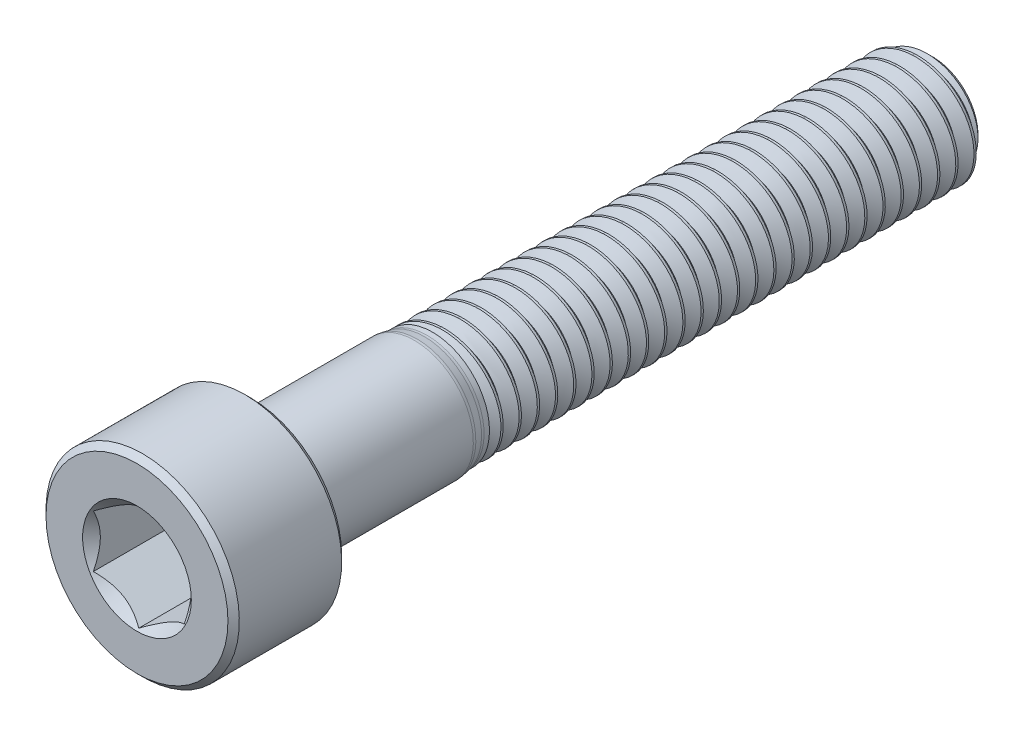
SolidWorks part; units mm, degrees
ref_plane "Front Plane" through (0, 0, 0) normal (0, 0, 1) x (1, 0, 0)
ref_plane "Top Plane" through (0, 0, 0) normal (0, 1, 0) x (1, 0, 0)
ref_plane "Right Plane" through (0, 0, 0) normal (1, 0, 0) x (0, 0, -1)
sketch "Sketch1" plane through (0, 0, 0) normal (1, 0, 0) x (0, 0, -1)
  line L0 (-17.5, 0) -> (17.5, 0) construction
  line L1 (17.5, 0) -> (17.5, 1.9804) construction
  line L2 (17.5, 1.9804) -> (16.9804, 2.5) construction
  line L3 (16.9804, 2.5) -> (16.9, 2.5) construction
  line L4 (16.9, 2.5) -> (-12.5, 2.5) construction
  line L5 (-12.5, 2.5) -> (-12.5, 4.25) construction
  line L6 (-12.5, 4.25) -> (-17.5, 4.25) construction
  line L7 (-17.5, 4.25) -> (-17.5, 0) construction
  line L8 (17.5, 1.9804) -> (17.5, 2.5) construction
  line L9 (17.45, 2.5866) -> (17.85, 1.8938) construction
  line L10 (17.85, 1.8938) -> (18.25, 2.5866) construction
  line L11 (18.25, 2.5866) -> (17.45, 2.5866) construction
  line L12 (17.85, 2.5866) -> (17.85, 2.5) construction
  line L13 (17.85, 1.8938) -> (17.85, 1.9804) construction
  line L14 (17.8, 1.9804) -> (17.9, 1.9804) construction
  line L15 (17.5, 2.5) -> (18.2, 2.5) construction
  line L16 (17.475, 2.5433) -> (18.225, 2.5433) construction
  line L17 (17.5, 0) -> (17.5, -2.5) construction
  line L18 (-12.75, 4.25) -> (-12.5, 4) construction
  line L19 (-17.25, 4.25) -> (-17.5, 4) construction
  line L20 (-12.5, 2.5) -> (-12.5, 0) construction
  line L21 (-12.5, 1.25) -> (-2.5, 1.25) construction
  line L22 (-2.5, 1.25) -> (7.5, 1.25) construction
  line L23 (7.5, 1.25) -> (17.5, 1.25) construction
  line L24 (-2.5, 1.25) -> (-2.5, 2.5) construction
  line L25 (-2.5, 2.5) -> (-2.5, 4.25) construction
  line L26 (7.5, 1.25) -> (7.5, 4.25) construction
  point P0 (-17.5, 2)
  point P3 (15.5, 2.5)
  point P4 (0, 0)
  point P18 (7.5, 2.5)
  point P22 (17.85, 1.9804)
  point P24 (16.9, 2.5)
  point P25 (17.85, 2.5)
  point P28 (17.85, 2.5433)
  point P29 (15.5, -2.5)
  point P30 (-2.5, 2.5)
  point P31 (-15, 4.25)
  point P37 (-13.375, 4.25)
  point P38 (-17.125, 4.25)
  point P45 (-2.5, 1.25)
  point P46 (7.5, 1.25)
  point P49 (-4.5, 2.5)
  dimension "D1" = 45
  dimension "D7" = 0.25
  dimension "D8" = 0.25
  dimension "D9" = 0.25
  dimension "D10" = 0.125
  dimension "D11" = 0.625
  dimension "Drive Size" = 4
  dimension "Head Diameter" = 8.5
  dimension "Head Height" = 5
  dimension "Thread Pitch" = 0.8
  dimension "Thread Size" = 5
  dimension "Length" = 30
  dimension "D12" = 0.6
  dimension "D4" = 2
  dimension "Minimum Thread Length" = 22
  dimension "D3" = 8
sketch "Sketch2" plane through (0, 0, 0) normal (1, 0, 0) x (0, 0, -1)
  line L0 (-17.5, 0) -> (-17.5, 4)
  line L1 (-17.25, 4.25) -> (-12.75, 4.25)
  line L2 (-12.5, 4) -> (-12.5, 2.8366)
  line L4 (16.9804, 2.5) -> (17.5, 1.9804)
  line L5 (17.5, 1.9804) -> (17.5, 0)
  line L6 (-12.5, 4.25) -> (-17.5, 4.25) construction
  line L7 (17.5, 0) -> (-17.5, 0)
  line L8 (-17.25, 4.25) -> (-17.5, 4) construction
  line L10 (-17.25, 4.25) -> (-17.5, 4)
  line L14 (-12.75, 4.25) -> (-12.5, 4) construction
  line L16 (-12.75, 4.25) -> (-12.5, 4)
  line L17 (-12.5, 2.5) -> (-12.5, 4.25) construction
  line L18 (-12.25, 2.5866) -> (-5.2969, 2.5866)
  line L19 (-4.7384, 2.5) -> (16.9804, 2.5)
  line L20 (16.9, 2.5) -> (-12.5, 2.5) construction
  line L21 (-5.175, 2.5746) -> (-4.8604, 2.512)
  line L22 (18.25, 2.5866) -> (17.45, 2.5866) construction
  arc A1 (-12.5, 2.8366) -> (-12.25, 2.5866) centre (-12.25, 2.8366) ccw
  arc A2 (-5.2969, 2.5866) -> (-5.175, 2.5746) centre (-5.2969, 1.9616) cw
  arc A3 (-4.8604, 2.512) -> (-4.7384, 2.5) centre (-4.7384, 3.125) ccw
  point P39 (-4.8, 2.5)
  dimension "D3" = 0.25
  dimension "D6" = 0.625
  dimension "D4" = 11.25
  dimension "D5" = 0.3
revolve "Revolve1" add sketch "Sketch2" angle 360 about L7
sketch "Sketch3" plane through (0, 0, 17.5) normal (0, 0, 1) x (1, 0, 0)
  line L1 (2, -1.1547) -> (2, 1.1547)
  line L2 (2, 1.1547) -> (0, 2.3094)
  line L3 (0, 2.3094) -> (-2, 1.1547)
  line L4 (-2, 1.1547) -> (-2, -1.1547)
  line L5 (-2, -1.1547) -> (0, -2.3094)
  line L6 (0, -2.3094) -> (2, -1.1547)
  circle A0 centre (0, 0) radius 2 construction
  circle A1 centre (0, 0) radius 4.25 construction
  circle A2 centre (0, 0) radius 4.25 construction
  circle A3 centre (0, 0) radius 2.3094 construction
  dimension "D1" = 4.6188
extrude "Cut-Extrude1" cut sketch "Sketch3" against normal offset from surface (4 mm away) 1 up to face at (0, 4, 12.5)
sketch "Sketch4" plane through (0, 0, 17.5) normal (0, 0, 1) x (1, 0, 0)
  circle A0 centre (0, 0) radius 2.3902
  dimension "D1" = 4.7805
extrude "Cut-Extrude2" cut sketch "Sketch4" against normal up to vertex (2.5 mm away) draft 45 up to point (0, 4.25, 15)
sketch "Sketch11" plane through (0, 0, 0) normal (1, 0, 0) x (0, 0, -1)
  line L0 (-17.5, 0) -> (17.5, 0) construction
  line L1 (-17.5, 0) -> (17.5, 0) construction
  line L2 (-11.5, 0) -> (-11.5, 2.5) construction
  line L3 (16.9, 2.5) -> (-12.5, 2.5) construction
  line L4 (-6.2969, 0) -> (-6.2969, 2.5) construction
  point P2 (-11.5, 0)
  point P3 (-6.2969, 0)
  dimension "D1" = 1
sketch "Sketch6" plane through (0, 0, -17.5) normal (0, 0, -1) x (-1, 0, 0)
  circle A0 centre (0, 0) radius 2.5
curve "Helix/Spiral1" pitch 0.8 height 22.8 radius 2.5 centre (0, 0, -17.5) axis (0, 0, 1) start towards (0, 1, 0)
sketch "Sketch10" plane through (0, 0, 0) normal (1, 0, 0) x (0, 0, -1)
  line L0 (-4.5, -2.5) -> (-4.5, 2.5)
  line L2 (-17.5, 0) -> (17.5, 0) construction
  point P3 (-4.5, 0)
split "Split1" trim tools "Sketch10" bodies to split 106 resulting bodies 114 115
sketch "Sketch7" plane through (0, 0, 0) normal (1, 0, 0) x (0, 0, -1)
  line L0 (17.475, 2.5433) -> (18.225, 2.5433)
  line L1 (18.225, 2.5433) -> (17.9, 1.9804)
  line L2 (17.9, 1.9804) -> (17.8, 1.9804)
  line L3 (17.8, 1.9804) -> (17.475, 2.5433)
sweep "Cut-Sweep1" cut profiles "Sketch7" path "Helix/Spiral1" align with end faces yes
sketch "Sketch8" plane through (0, 0, 0) normal (1, 0, 0) x (0, 0, -1)
  line L0 (-12.5, 0) -> (-12.5, 2.5)
  line L2 (-12.5, 2.5) -> (-4.5, 2.5)
  line L4 (-4.5, 2.5) -> (-3.0566, 0)
  line L5 (-3.0566, 0) -> (-12.5, 0)
  line L6 (16.9, 2.5) -> (-12.5, 2.5) construction
  line L7 (-17.5, 0) -> (17.5, 0) construction
  dimension "D1" = 60
  dimension "D2" = 22
revolve "Revolve2" add sketch "Sketch8" angle 360 about L5
equation "\"D2@Sketch1\" = \"Thread Pitch@Sketch1\" / 8"
equation "\"D4@Helix/Spiral1\" = \"Thread Pitch@Sketch1\""
equation "\"D7@Sketch1\" = \"Head Height@Sketch1\" * .05"
equation "\"D8@Sketch1\"=\"D7@Sketch1\""
equation "\"D9@Sketch1\"=\"D7@Sketch1\""
equation "\"D10@Sketch1\"=\"D7@Sketch1\"/2"
equation "\"D11@Sketch1\"=\"D10@Sketch1\"*5"
equation "\"D4@Sketch1\"=\"Thread Pitch@Sketch1\"*2.5"
equation "\"D12@Sketch1\"=\"Thread Pitch@Sketch1\"*.75"
equation "\"D3@Helix/Spiral1\"=\"Minimum Thread Length@Sketch1\"+\"Thread Pitch@Sketch1\""
equation "\"D2@Sketch8\"=\"Minimum Thread Length@Sketch1\""
equation "\"D3@Sketch2\" = \"Thread Size@Sketch1\" * 0.05"
equation "\"D5@Sketch2\"=\"D12@Sketch1\"*0.5"
equation "\"D6@Sketch2\" = \"Thread Size@Sketch1\" * 0.125"
equation "\"D1@Sketch11\"=\"D3@Sketch1\"*0.125"
equation "\"D2@Sketch11\"=\"D1@Sketch11\""
equation "\"D1@Sketch4\"=\"D1@Sketch3\"*1.035"
